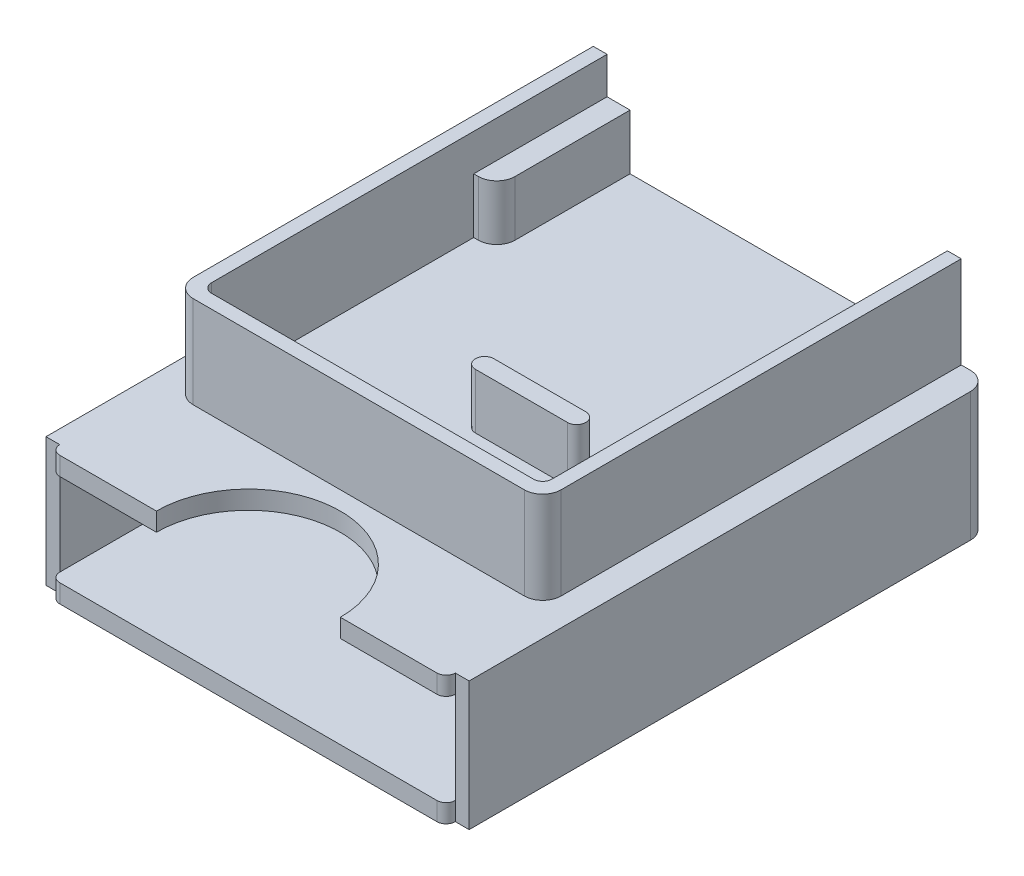
SolidWorks part; units mm, degrees
ref_plane "Front Plane" through (0, 0, 0) normal (0, 0, 1) x (1, 0, 0)
ref_plane "Top Plane" through (0, 0, 0) normal (0, 1, 0) x (1, 0, 0)
ref_plane "Right Plane" through (0, 0, 0) normal (1, 0, 0) x (0, 0, -1)
sketch "Sketch10" plane through (0, 0, 0) normal (0, 1, 0) x (1, 0, 0)
  line L0 (-10.75, -13.5) -> (-11.5, -13.5)
  line L1 (10.5, 14.75) -> (-10.5, 14.75)
  line L2 (11.5, 13.75) -> (11.5, -13.75)
  line L3 (10.5, -14.75) -> (-10.5, -14.75)
  line L4 (-11.5, 13.75) -> (-11.5, -13.75)
  line L5 (4.75, 16.25) -> (-4.75, 16.25)
  line L6 (4.75, 16.25) -> (4.75, 14.75)
  line L7 (10.25, 14) -> (-10.25, 14)
  line L8 (10.75, 13.5) -> (10.75, -13.5)
  line L9 (10.25, -14) -> (-10.25, -14)
  line L10 (-10.75, 13.5) -> (-10.75, -13.5)
  line L11 (4.75, 14.75) -> (-4.75, 14.75)
  line L12 (-4.75, 16.25) -> (-4.75, 14.75)
  line L13 (10.75, -13.5) -> (11.5, -13.5)
  arc A0 (-11.5, -13.75) -> (-10.5, -14.75) centre (-10.5, -13.75) ccw
  arc A1 (11.5, -13.75) -> (10.5, -14.75) centre (10.5, -13.75) cw
  arc A2 (11.5, 13.75) -> (10.5, 14.75) centre (10.5, 13.75) ccw
  arc A3 (-11.5, 13.75) -> (-10.5, 14.75) centre (-10.5, 13.75) cw
  arc A4 (-10.75, 13.5) -> (-10.25, 14) centre (-10.25, 13.5) cw
  arc A5 (-10.75, -13.5) -> (-10.25, -14) centre (-10.25, -13.5) ccw
  arc A6 (10.25, -14) -> (10.75, -13.5) centre (10.25, -13.5) ccw
  arc A7 (10.75, 13.5) -> (10.25, 14) centre (10.25, 13.5) ccw
  point P0 (0, 0)
  point P6 (0, 0)
extrude "Boss-Extrude23" add sketch "Sketch10" along normal blind 1 contours L8 A7 L7 A4 L10 A5 L9 A6 | A3 L4 A0 L3 A1 L2 A2 L1 A7 L8 A6 L9 A5 L10 A4 L7 region at (-11.125, 0, 13.1357) region at (0, 0, 0)
extrude "Boss-Extrude27" add sketch "Sketch10<6>" along normal blind 6 contours A7 L8 L13 L2 A2 L1 A3 L4 L0 L10 A4 L7 region at (-11.125, 0, 13.1357)
sketch "Sketch10<6>" plane through (0, 0, 0) normal (0, 1, 0) x (1, 0, 0) same geometry as "Sketch10"
extrude "Boss-Extrude28" add sketch "Sketch10<7>" along normal blind 1 from offset 6 contours A7 L8 L13 L2 A2 L1 A3 L4 L0 L10 A4 L7 | L8 A7 L7 A4 L10 A5 L9 A6 region at (-11.125, 0, 13.1357) region at (0, 0, 0)
sketch "Sketch10<7>" plane through (0, 0, 0) normal (0, 1, 0) x (1, 0, 0) same geometry as "Sketch10"
sketch "Sketch13" plane through (0, 7, 0) normal (0, 1, 0) x (1, 0, 0)
  line L0 (10.25, -14) -> (-10.25, -14) construction
  line L1 (-5, -14) -> (5, -14)
  arc A0 (5, -14) -> (-5, -14) centre (0, -14) ccw
extrude "Cut-Extrude9" cut sketch "Sketch13" against normal blind 1
sketch "Sketch15" plane through (0, 0, -14.75) normal (0, 0, -1) x (-1, 0, 0)
  line L1 (5, 1) -> (-5, 1)
  line L2 (5, 1) -> (5, 3)
  line L3 (5, 3) -> (-5, 3)
  line L4 (-5, 1) -> (-5, 3)
extrude "Cut-Extrude11" cut sketch "Sketch15" against normal blind 10
sketch "Sketch17" plane through (0, 7, 0) normal (0, 1, 0) x (1, 0, 0)
  line L0 (-9.25, 14.75) -> (-10, 14.75)
  line L1 (-9, 23) -> (9, 23)
  line L2 (-10, 22) -> (-10, -7)
  line L3 (-9, -8) -> (9, -8)
  line L4 (10, 22) -> (10, -7)
  line L5 (-8.75, 22.25) -> (8.75, 22.25)
  line L6 (-9.25, 21.75) -> (-9.25, -6.75)
  line L7 (-8.75, -7.25) -> (8.75, -7.25)
  line L8 (9.25, 21.75) -> (9.25, -6.75)
  line L9 (10.5, 14.75) -> (-10.5, 14.75) construction
  line L10 (9.25, 14.75) -> (10, 14.75)
  arc A0 (-9.25, -6.75) -> (-8.75, -7.25) centre (-8.75, -6.75) ccw
  arc A1 (8.75, -7.25) -> (9.25, -6.75) centre (8.75, -6.75) ccw
  arc A2 (9.25, 21.75) -> (8.75, 22.25) centre (8.75, 21.75) ccw
  arc A3 (-8.75, 22.25) -> (-9.25, 21.75) centre (-8.75, 21.75) ccw
  arc A4 (-10, -7) -> (-9, -8) centre (-9, -7) ccw
  arc A5 (-9, 23) -> (-10, 22) centre (-9, 22) ccw
  arc A6 (9, 23) -> (10, 22) centre (9, 22) cw
  arc A7 (10, -7) -> (9, -8) centre (9, -7) cw
  line M7 (10.5, 14.75) -> (-10.5, 14.75)
extrude "Boss-Extrude30" add sketch "Sketch17" along normal blind 5 contours A7 L4 L8 A1 L7 A0 L6 L2 A4 L3 M7 region at (-9.5529, 7, -4)
sketch "Sketch18" plane through (0, 7, 0) normal (0, 1, 0) x (1, 0, 0)
  line L0 (9, 7.5) -> (9.25, 7.5)
  line L1 (5, -1.1568) -> (0, -1.1568) construction
  line L2 (5, -1.6568) -> (0, -1.6568)
  line L3 (5, -0.6568) -> (0, -0.6568)
  line L4 (9.25, 14.75) -> (9.25, -6.75) construction
  line L5 (9.25, 7.5) -> (9.25, 14.75)
  line L9 (-9.25, 7.5) -> (-9, 7.5)
  line L10 (-9.25, 14.75) -> (-9.25, -6.75) construction
  line L11 (-8, 8.5) -> (-8, 14.75)
  line L12 (9.25, 14.75) -> (-9.25, 14.75) construction
  line L13 (-8, 14.75) -> (-9.25, 14.75)
  line L14 (-9.25, 14.75) -> (-9.25, 7.5)
  line L15 (9.25, 14.75) -> (9.25, -6.75) construction
  line L16 (9.25, 14.75) -> (8, 14.75)
  line L17 (8, 14.75) -> (8, 8.5)
  arc A0 (5, -1.6568) -> (5, -0.6568) centre (5, -1.1568) ccw
  arc A1 (0, -0.6568) -> (0, -1.6568) centre (0, -1.1568) ccw
  arc A2 (9, 7.5) -> (8, 8.5) centre (9, 8.5) cw
  arc A3 (-8, 8.5) -> (-9, 7.5) centre (-9, 8.5) cw
  point P4 (2.5, -1.1568)
  line M1 (9.25, 14.75) -> (-9.25, 14.75)
  line M2 (-9.25, 14.75) -> (-9.25, -6.75)
  line M6 (9.25, -6.75) -> (9.25, 14.75)
extrude "Boss-Extrude31" add sketch "Sketch18" along normal blind 3 contours A3 L11 L9 M1 M2 | A2 L0 L17 M6 M1 | L2 A1 L3 A0 region at (8.6347, 7, -11.2075) region at (-8.6347, 7, -11.2075)
